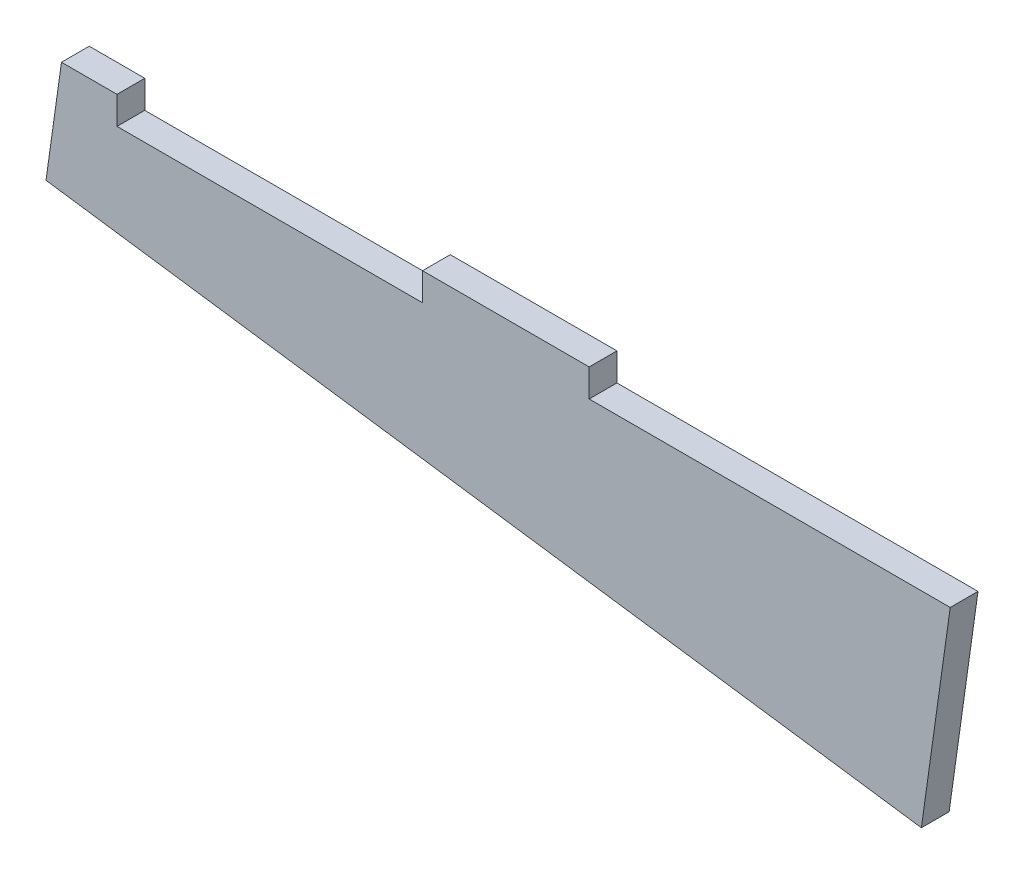
SolidWorks part; units mm, degrees
ref_plane "Front Plane" through (0, 0, 0) normal (0, 0, 1) x (1, 0, 0)
ref_plane "Top Plane" through (0, 0, 0) normal (0, 1, 0) x (1, 0, 0)
ref_plane "Right Plane" through (0, 0, 0) normal (1, 0, 0) x (0, 0, -1)
sketch "Sketch1" plane through (0, 0, 0) normal (0, 0, 1) x (1, 0, 0)
  line L0 (-194.0664, -59.2629) -> (-181.3664, -59.2629)
  line L4 (-181.3664, -59.2629) -> (-181.3664, -65.6129)
  line L5 (-181.3664, -65.6129) -> (-111.5164, -65.6129)
  line L6 (-111.5164, -65.6129) -> (-111.5164, -59.2629)
  line L7 (-111.5164, -59.2629) -> (-73.4164, -59.2629)
  line L8 (-73.4164, -59.2629) -> (-73.4164, -65.6129)
  line L9 (-73.4164, -65.6129) -> (9.1336, -65.6129)
  line L10 (9.1336, -65.6129) -> (2.5379, -112.5435)
  line L11 (2.5379, -112.5435) -> (-197.6014, -84.4157)
  line L12 (-197.6014, -84.4157) -> (-194.0664, -59.2629)
  line L13 (-1252.3476, 75.5417) -> (-858.6476, 20.2107) construction
  point P2 (-62.7286, -30.0583)
  dimension "D1" = 12.7
  dimension "D2" = 6.35
  dimension "D3" = 69.85
  dimension "D4" = 38.1
  dimension "D5" = 82.55
  dimension "D6" = 25.4
extrude "Boss-Extrude1" add sketch "Sketch1" against normal blind 6.35
